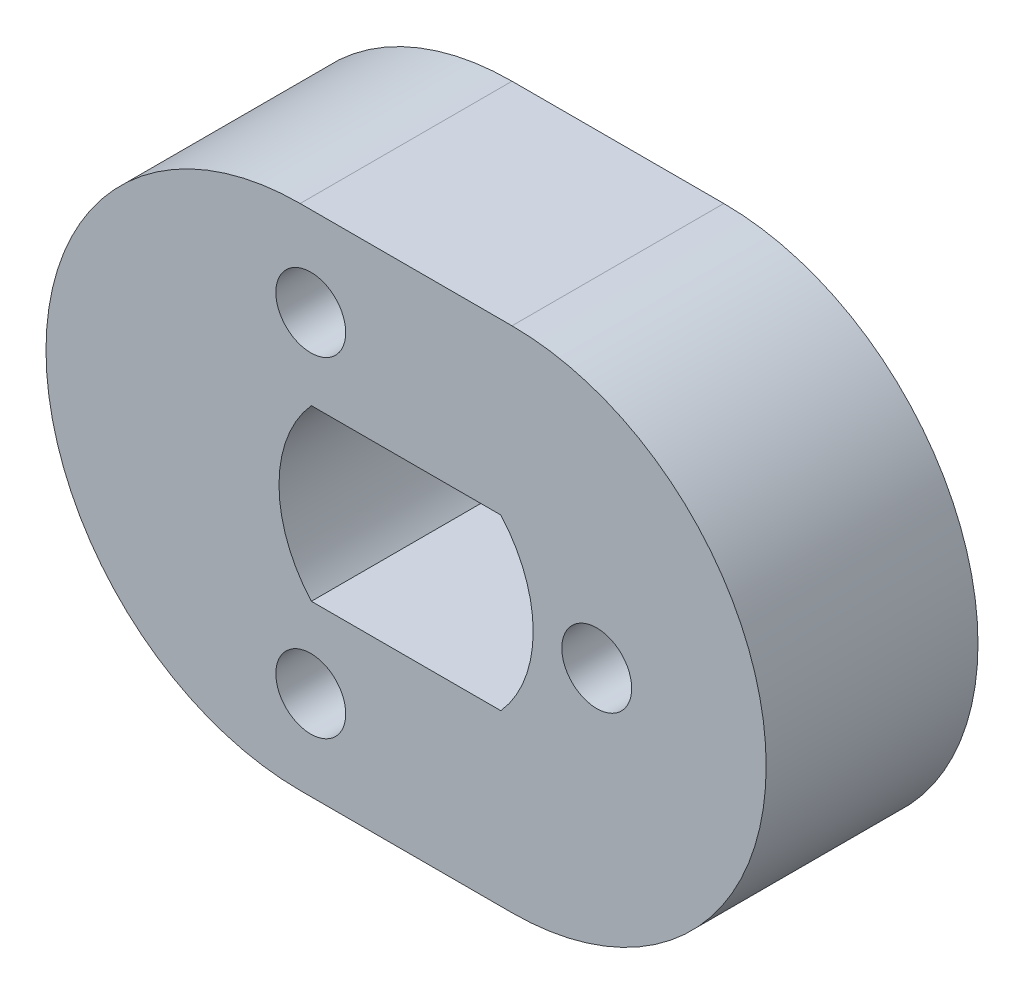
SolidWorks part; units mm, degrees
ref_plane "Front Plane" through (0, 0, 0) normal (0, 0, 1) x (1, 0, 0)
ref_plane "Top Plane" through (0, 0, 0) normal (0, 1, 0) x (1, 0, 0)
ref_plane "Right Plane" through (0, 0, 0) normal (1, 0, 0) x (0, 0, -1)
sketch "Sketch1" plane through (0, 0, 0) normal (0, 0, 1) x (1, 0, 0)
  line L0 (0, 0) -> (10, 0) construction
  line L1 (0, 12) -> (10, 12)
  line L2 (0, -12) -> (10, -12)
  arc A0 (0, 12) -> (0, -12) centre (0, 0) ccw
  arc A1 (10, -12) -> (10, 12) centre (10, 0) ccw
  circle A2 centre (5, 0) radius 6
  point P3 (5, 0)
  dimension "D1" = 12
  dimension "D2" = 10
  dimension "D3" = 12
extrude "Boss-Extrude1" add sketch "Sketch1" along normal blind 10
sketch "Sketch2" plane through (0, 0, 10) normal (0, 0, 1) x (1, 0, 0)
  circle A0 centre (5, 0) radius 9
  point P3 (14, 0)
  dimension "D1" = 18
hole_wizard "M4 Tapped Hole1" positions "3DSketch1" profile "Sketch3" tap size "M4" standard "ISO" end condition through all
sketch3d "3DSketch1"
  point P0 (14, 0, 10)
sketch "Sketch3" plane through (14, 0, 10) normal (1, 0, 0) x (0, -1, 0)
  line L0 (0, 0) -> (0, 10)
  line L1 (0, 10) -> (1.65, 10)
  line L2 (1.65, 10) -> (1.65, 0)
  line L5 (1.65, 0) -> (0, 0)
  line L11 (0, -6.35) -> (0, 107.95) construction
  dimension "Thru Tap Drill Dia." = 3.3
  dimension "Thru Tap Drill Depth" = 10
cosmetic thread "Hole Thread2" parameters "D2"=4
pattern_circular "CirPattern1" count 3 every 120 about axis through (5, 0, 10) along (0, 0, 1) of "M4 Tapped Hole1"
sketch "Sketch4" plane through (0, 0, 10) normal (0, 0, 1) x (1, 0, 0)
  line L0 (0.5279, 4) -> (9.4721, 4)
  line L1 (0.5279, -4) -> (9.4721, -4)
  circle A0 centre (5, 0) radius 6 construction
  arc A1 (9.4721, 4) -> (9.4721, -4) centre (5, 0) ccw
  circle M10 centre (5, 0) radius 6
  dimension "D1" = 8
  dimension "D2" = 4
extrude "Boss-Extrude2" add sketch "Sketch4" against normal blind 10 contours L0 M10 | L1 M10 region at (5, 4.8127, 10) region at (5, -4.8127, 10)
